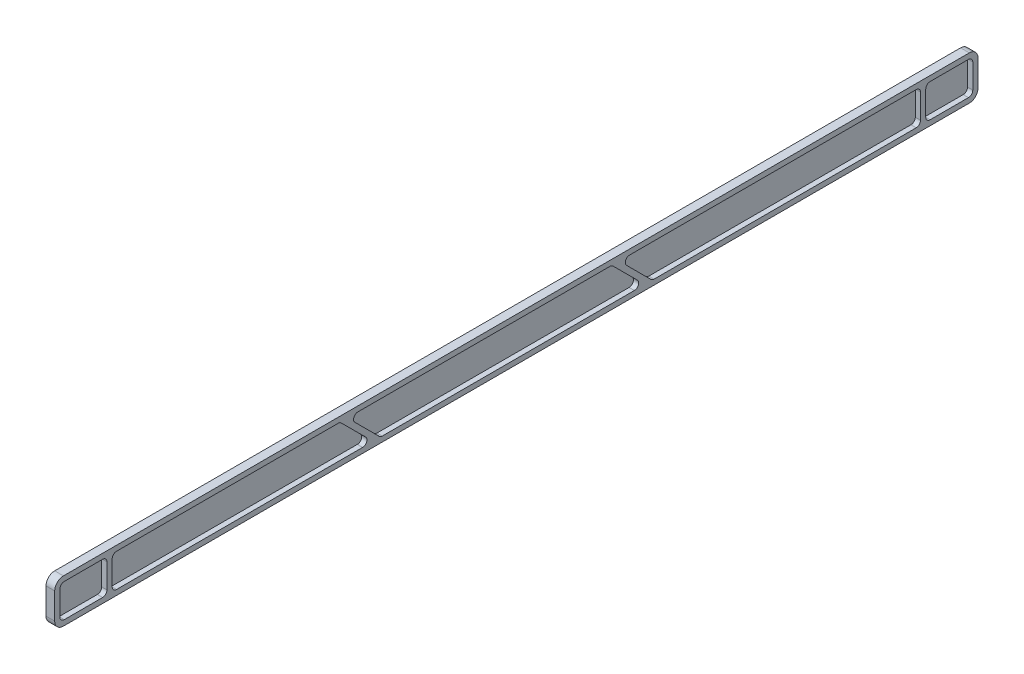
SolidWorks part; units mm, degrees
material "moto_black"
ref_plane "Front Plane" through (0, 0, 0) normal (0, 0, 1) x (1, 0, 0)
ref_plane "Top Plane" through (0, 0, 0) normal (0, 1, 0) x (1, 0, 0)
ref_plane "Right Plane" through (0, 0, 0) normal (1, 0, 0) x (0, 0, -1)
sketch "Sketch1" plane through (0, 0, 0) normal (1, 0, 0) x (0, 0, -1)
  line L0 (-262, -9.5) -> (-262, 9.5)
  line L1 (-265, -12.5) -> (265, -12.5)
  line L2 (-265, -12.5) -> (-265, 12.5)
  line L3 (-265, 12.5) -> (265, 12.5)
  line L4 (265, -12.5) -> (265, 12.5)
  line L5 (-265, -12.5) -> (265, 12.5) construction
  line L6 (-265, 12.5) -> (265, -12.5) construction
  line L7 (-262, 9.5) -> (262, 9.5)
  line L8 (262, -9.5) -> (262, 9.5)
  line L9 (-262, -9.5) -> (262, -9.5)
  line L10 (-232, 9.5) -> (-232, -9.5)
  line L11 (-235, 9.5) -> (-235, -9.5)
  line L12 (0, 0) -> (0, -25.8706)
  line L13 (235, 9.5) -> (235, -9.5)
  line L14 (232, 9.5) -> (232, -9.5)
  line L15 (-97, 9.5) -> (-78, -9.5)
  line L16 (59, 9.5) -> (78, -9.5)
  line L17 (-82.2426, -9.5) -> (-101.2426, 9.5)
  line L18 (54.7574, 9.5) -> (73.7574, -9.5)
  point P0 (0, 0)
  dimension "D1" = 530
  dimension "D2" = 25
  dimension "D4" = 30
  dimension "D5" = 3
  dimension "D6" = 45
  dimension "D7" = 45
  dimension "D8" = 154
  dimension "D9" = 154
  dimension "D11" = 3
  dimension "D10" = 3
  dimension "D3" = 3
extrude "Boss-Extrude3" add sketch "Sketch1" against normal blind 2 contours L11 L7 L0 L9 | L9 L0 L7 L8 L1 L4 L3 L2 | L7 L11 L9 L10 | L9 L17 L7 L10 | L17 L9 L15 L7 | L18 L7 L15 L9 | L7 L18 L9 L16 | L7 L16 L9 L14 | L7 L14 L9 L13 | L7 L13 L9 L8 region at (0, -11.9694, 132.5) region at (0, 0, 248.5) region at (0, 0, 233.5) region at (0, -0.2145, 161.7641) region at (0, 0, 89.6213) region at (0, 0, 11.6213) region at (0, 0, -66.3787) region at (0, 0.184, -150.158) region at (0, 0, -233.5) region at (0, 0, -248.5)
extrude "Boss-Extrude4" add sketch "Sketch1<5>" along normal blind 3 contours L9 L0 L7 L8 L1 L4 L3 L2 | L7 L11 L9 L10 | L17 L9 L15 L7 | L7 L18 L9 L16 | L7 L14 L9 L13 region at (0, -11.9694, 132.5) region at (0, 0, 233.5) region at (0, 0, 89.6213) region at (0, 0, -66.3787) region at (0, 0, -233.5)
sketch "Sketch1<5>" plane through (0, 0, 0) normal (1, 0, 0) x (0, 0, -1) same geometry as "Sketch1"
fillet "Fillet1" radius 5 4 edges at (0.5, 12.5, -265) (0.5, -12.5, -265) (0.5, 12.5, 265) (0.5, -12.5, 265)
fillet "Fillet2" radius 2.5 4 edges at (1.5, -9.5, -262) (1.5, 9.5, -262) (1.5, -9.5, 262) (1.5, 9.5, 262)
fillet "Fillet3" radius 2.5 16 edges at (1.5, -9.5, -235) (1.5, 9.5, -235) (1.5, 9.5, -232) (1.5, -9.5, -232) (1.5, 9.5, -59) (1.5, -9.5, -78) (1.5, -9.5, -73.7574) (1.5, 9.5, -54.7574) (1.5, 9.5, 97) (1.5, -9.5, 78) (1.5, -9.5, 82.2426) (1.5, 9.5, 101.2426) (1.5, -9.5, 232) (1.5, 9.5, 232) (1.5, -9.5, 235) (1.5, 9.5, 235)
